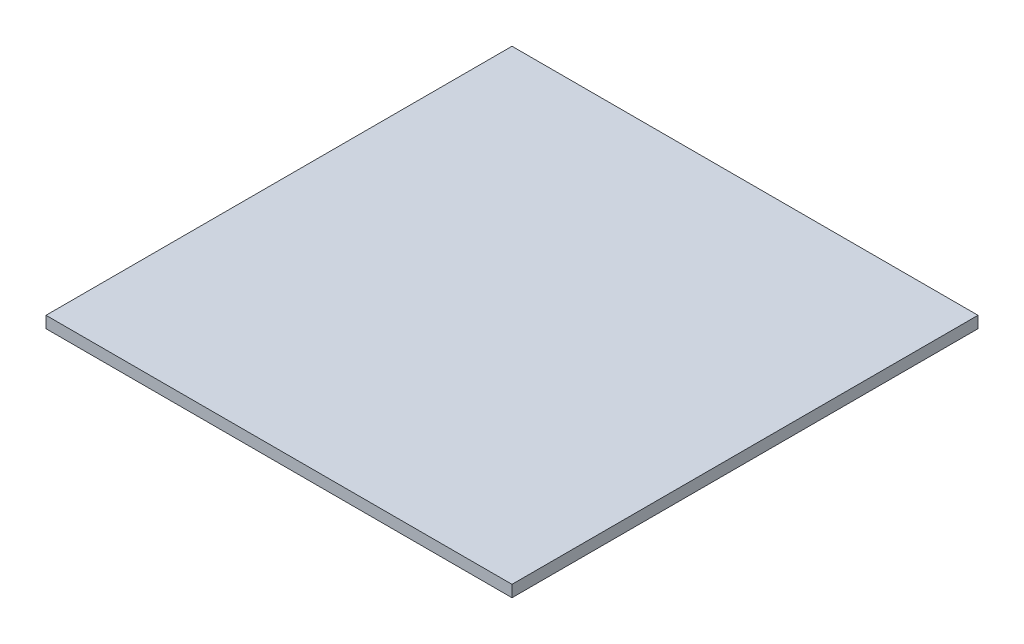
SolidWorks part; units mm, degrees
ref_plane "Front Plane" through (0, 0, 0) normal (0, 0, 1) x (1, 0, 0)
ref_plane "Top Plane" through (0, 0, 0) normal (0, 1, 0) x (1, 0, 0)
ref_plane "Right Plane" through (0, 0, 0) normal (1, 0, 0) x (0, 0, -1)
sketch "Sketch1" plane through (0, 0, 0) normal (0, 1, 0) x (1, 0, 0)
  line L0 (0, 0) -> (254, 0)
  line L1 (254, 0) -> (254, 254)
  line L2 (254, 254) -> (0, 254)
  line L3 (0, 254) -> (0, 0)
  dimension "D1" = 254
  dimension "D2" = 254
extrude "Boss-Extrude1" add sketch "Sketch1" along normal blind 6.35
sketch "Sketch2" plane through (0, 6.35, 0) normal (0, 1, 0) x (1, 0, 0)
  line L0 (127, 254) -> (127, 0) construction
  line L1 (254, 254) -> (0, 254) construction
  line L2 (0, 0) -> (254, 0) construction
  line L3 (228.6, 127) -> (25.4, 127) construction
  line L4 (228.6, 127) -> (228.6, 114.3) construction
  line L5 (25.4, 127) -> (25.4, 114.3) construction
  point P8 (127, 127)
  point P9 (127, 127)
  dimension "D1" = 203.2
  dimension "D2" = 12.7
  dimension "D3" = 12.7
equation "\"wall_thickness\" = 0.125in"
equation "\"base_thickness\" = 0.25in"
equation "\"D1@Boss-Extrude1\"=\"base_thickness\""
